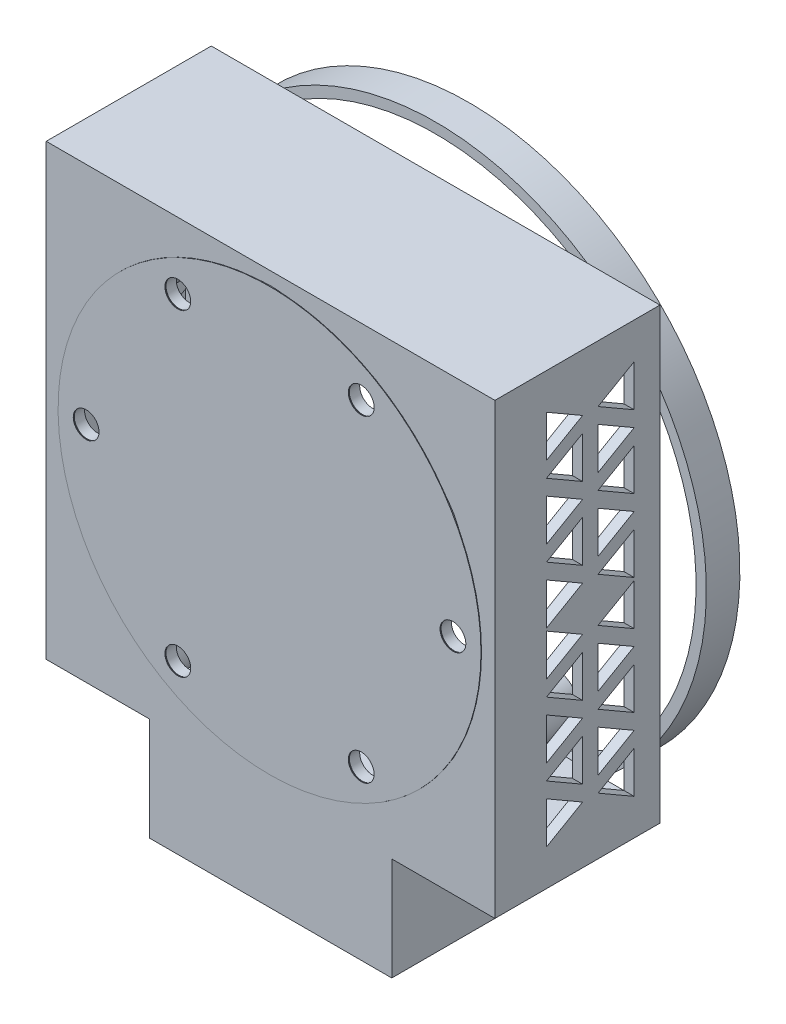
SolidWorks part; units mm, degrees
ref_plane "Front Plane" through (0, 0, 0) normal (0, 0, 1) x (1, 0, 0)
ref_plane "Top Plane" through (0, 0, 0) normal (0, 1, 0) x (1, 0, 0)
ref_plane "Right Plane" through (0, 0, 0) normal (1, 0, 0) x (0, 0, -1)
sketch "Sketch1" plane through (0, 0, 0) normal (0, 0, 1) x (1, 0, 0)
  circle A0 centre (0, 0) radius 41
  dimension "D1" = 82
extrude "Boss-Extrude1" add sketch "Sketch1" along normal blind 0.1 contours A0
sketch "Sketch2" plane through (0, 0, 0) normal (0, 0, -1) x (-1, 0, 0)
  line L0 (-35.56, 0) -> (35.56, 0) construction
  line L1 (0, 0) -> (0, -41) construction
  line L2 (0, 0) -> (0, 41) construction
  line L3 (0, -30.7959) -> (17.78, -30.7959) construction
  line L4 (0, -30.7959) -> (-17.78, -30.7959) construction
  circle A0 centre (-35.56, 0) radius 2.5
  circle A1 centre (35.56, 0) radius 2.5
  circle A2 centre (0, 0) radius 38.06 construction
  circle A3 centre (0, 0) radius 33.06 construction
  circle A4 centre (-17.78, -30.7959) radius 2.5
  circle A5 centre (17.78, -30.7959) radius 2.5
  circle A6 centre (0, 0) radius 41 construction
  circle A7 centre (-17.78, 30.7959) radius 2.5
  circle A8 centre (17.78, 30.7959) radius 2.5
  point P4 (0, 0)
  dimension "D2" = 5
  dimension "D3" = 66.12
  dimension "D4" = 76.12
  dimension "D6" = 5
  dimension "D7" = 5
  dimension "D1" = 71.12
  dimension "D5" = 35.56
extrude "Cut-Extrude1" cut sketch "Sketch2" against normal blind 10
sketch "Sketch3" plane through (0, 0, 0) normal (0, 0, -1) x (-1, 0, 0)
  circle A1 centre (0, 0) radius 47.5 construction
  arc A2 (22.2693, -27.7235) -> (12.8746, -33.1475) centre (17.78, -30.7959) ccw
  circle A3 centre (0, 0) radius 42.5 construction
  arc A5 (-12.8746, -33.1475) -> (-22.2693, -27.7235) centre (-17.78, -30.7959) ccw
  circle A12 centre (0, 0) radius 41
  arc A13 (-35.1439, -5.4241) -> (-35.1439, 5.4241) centre (-35.56, 0) ccw
  arc A14 (-22.2693, 27.7235) -> (-12.8746, 33.1475) centre (-17.78, 30.7959) ccw
  arc A15 (12.8746, 33.1475) -> (22.2693, 27.7235) centre (17.78, 30.7959) ccw
  arc A16 (35.1439, 5.4241) -> (35.1439, -5.4241) centre (35.56, 0) ccw
  arc A17 (22.2693, -27.7235) -> (35.1439, -5.4241) centre (22.9665, -13.2597) ccw
  circle A19 centre (0, 0) radius 41 construction
  arc A25 (-22.2693, 27.7235) -> (-35.1439, 5.4241) centre (-22.9665, 13.2597) ccw
  arc A26 (35.1439, 5.4241) -> (22.2693, 27.7235) centre (22.9665, 13.2597) ccw
  arc A28 (-35.1439, -5.4241) -> (-22.2693, -27.7235) centre (-22.9665, -13.2597) ccw
  arc A29 (-12.8746, -33.1475) -> (12.8746, -33.1475) centre (0, -26.5195) ccw
  arc A30 (12.8746, 33.1475) -> (-12.8746, 33.1475) centre (0, 26.5195) ccw
  dimension "D1" = 95
  dimension "D2" = 85
extrude "Boss-Extrude3" add sketch "Sketch3" along normal blind 0.1 contours A15 A30 A14 A25 A13 A28 A5 A29 A2 A17 A16 A26 region at (0, 0, 0)
sketch "Sketch4" plane through (0, 0, -0.1) normal (0, 0, -1) x (-1, 0, 0)
  line L0 (-43.5, 43.5) -> (43.5, -43.5) construction
  line L1 (-43.5, 43.5) -> (43.5, 43.5)
  line L2 (-43.5, 43.5) -> (-43.5, -43.5)
  line L3 (-43.5, -43.5) -> (43.5, -43.5)
  line L4 (43.5, 43.5) -> (43.5, -43.5)
  line L5 (-43.5, -43.5) -> (43.5, 43.5) construction
  point P2 (0, 0)
  dimension "D1" = 87
  dimension "D2" = 87
extrude "Boss-Extrude4" add sketch "Sketch4" along normal blind 2
sketch "Sketch5" plane through (0, 0, -2.1) normal (0, 0, -1) x (-1, 0, 0)
  line L1 (-43.5, 43.5) -> (43.5, 43.5)
  line L2 (-43.5, 43.5) -> (-43.5, -43.5)
  line L3 (-43.5, -43.5) -> (43.5, -43.5)
  line L4 (43.5, 43.5) -> (43.5, -43.5)
  line L5 (-41.5, 41.5) -> (41.5, 41.5)
  line L6 (-41.5, 41.5) -> (-41.5, -41.5)
  line L7 (-41.5, -41.5) -> (41.5, -41.5)
  line L8 (41.5, 41.5) -> (41.5, -41.5)
  dimension "D1" = 2
  dimension "D2" = 2
  dimension "D3" = 2
  dimension "D4" = 2
extrude "Boss-Extrude5" add sketch "Sketch5" along normal blind 30
sketch "Sketch7" plane through (0, 0, -32.1) normal (0, 0, -1) x (-1, 0, 0)
  line L1 (-41.5, 41.5) -> (41.5, 41.5)
  line L2 (-41.5, 41.5) -> (-41.5, -41.5)
  line L3 (-41.5, -41.5) -> (41.5, -41.5)
  line L4 (41.5, 41.5) -> (41.5, -41.5)
  line L5 (-43.5, 43.5) -> (43.5, 43.5)
  line L6 (-43.5, 43.5) -> (-43.5, -43.5)
  line L7 (-43.5, -43.5) -> (43.5, -43.5)
  line L8 (43.5, 43.5) -> (43.5, -43.5)
extrude "Boss-Extrude6" add sketch "Sketch7" against normal up to surface (32 mm away) up to face at (0, 0, -0.1)
sketch "Sketch8" plane through (0, 0, -32.1) normal (0, 0, -1) x (-1, 0, 0)
  line L0 (-41.5, -41.5) -> (41.5, -41.5) construction
  line L1 (41.5, -41.5) -> (41.5, 41.5) construction
  line L2 (-41.5, 41.5) -> (-41.5, -41.5) construction
  line L3 (41.5, 41.5) -> (-41.5, 41.5) construction
  line L4 (-53, 0) -> (-41.5, 0) construction
  line L5 (-41.5, 41.5) -> (-41.5, -41.5) construction
  line L6 (0, 41.5) -> (0, 53) construction
  line L7 (41.5, 0) -> (53, 0) construction
  line L8 (0, -41.5) -> (0, -53) construction
  line L9 (-41.5, -41.5) -> (41.5, -41.5) construction
  circle A0 centre (-47, 0) radius 2
  circle A1 centre (47.25, 0) radius 2
  circle A2 centre (0, 47.25) radius 2
  circle A3 centre (0, -47.25) radius 2
  circle A4 centre (-47, 0) radius 6 construction
  circle A5 centre (0, 47.25) radius 5.75 construction
  circle A6 centre (0, 0) radius 53 construction
  circle A7 centre (47.25, 0) radius 5.75 construction
  circle A8 centre (0, -47.25) radius 5.75 construction
  parabola Q1 (-50, 50) -> (-50, -50) focus (155.3333, 0) apex (-53, 0) construction
  parabola Q3 (50, 50) -> (-50, 50) focus (0, -155.3333) apex (0, 53) construction
  parabola Q4 (50, -50) -> (50, 50) focus (-155.3333, 0) apex (53, 0) construction
  parabola Q5 (-50, -50) -> (50, -50) focus (0, 155.3333) apex (0, -53) construction
  point P10 (0, -41.5)
  point P13 (41.5, 0)
  point P16 (-41.5, 0)
  point P19 (0, 41.5)
  point P50 (0, -47.25)
  point P51 (47.25, 0)
  point P52 (0, 47.25)
  dimension "D1" = 106
  dimension "D2" = 4
  dimension "D3" = 4
  dimension "D4" = 4
  dimension "D5" = 4
  dimension "D6" = 6
sketch "Sketch11" plane through (0, 0, -2.1) normal (0, 0, -1) x (-1, 0, 0)
  line L2 (0, 38.94) -> (0, 41.5) construction
  line L3 (-38.985, 38.94) -> (38.985, 38.94) construction
  line L4 (-38.985, 38.94) -> (-38.985, -38.94) construction
  line L5 (-38.985, -38.94) -> (38.985, -38.94) construction
  line L6 (38.985, 38.94) -> (38.985, -38.94) construction
  line L7 (0, -38.94) -> (0, -41.5) construction
  line L8 (-41.5, -41.5) -> (41.5, -41.5) construction
  line L9 (-38.985, 0) -> (-41.5, 0) construction
  line L10 (-41.5, 41.5) -> (-41.5, -41.5) construction
  line L11 (38.985, 0) -> (41.5, 0) construction
  line L12 (41.5, -41.5) -> (41.5, 41.5) construction
  circle A0 centre (-34.985, 34.94) radius 2
  circle A1 centre (36.985, 20.64) radius 2
  circle A2 centre (28.745, -36.94) radius 2
  circle A3 centre (-34.985, -20.58) radius 2
  circle A4 centre (-34.985, -20.58) radius 5
  circle A5 centre (28.745, -36.94) radius 5
  circle A6 centre (36.985, 20.64) radius 5
  circle A7 centre (-34.985, 34.94) radius 5
  dimension "D1" = 4
  dimension "D2" = 71.97
  dimension "D3" = 57.58
  dimension "D9" = 4
  dimension "D10" = 4
  dimension "D4" = 4
  dimension "D5" = 63.73
  dimension "D6" = 55.52
  dimension "D7" = 4
  dimension "D8" = 14.3
extrude "Boss-Extrude7" add sketch "Sketch11" along normal blind 18
sketch "Sketch10" plane through (0, 0, 0.1) normal (0, 0, 1) x (1, 0, 0)
  circle A0 centre (-17.78, 30.7959) radius 2.5
  circle A1 centre (17.78, 30.7959) radius 2.5
  circle A2 centre (35.56, 0) radius 2.5
  circle A3 centre (17.78, -30.7959) radius 2.5
  circle A4 centre (-17.78, -30.7959) radius 2.5
  circle A5 centre (-35.56, 0) radius 2.5
extrude "Cut-Extrude3" cut sketch "Sketch10" against normal through all
sketch "Sketch13" plane through (0, -43.5, 0) normal (0, -1, 0) x (1, 0, 0)
  line L0 (-53, -32.1) -> (53, -32.1) construction
  line L1 (-23.5, -0.1) -> (23.5, -0.1)
  line L2 (-23.5, -0.1) -> (-23.5, -32.1)
  line L3 (-23.5, -32.1) -> (23.5, -32.1)
  line L4 (23.5, -0.1) -> (23.5, -32.1)
  line L5 (43.5, -32.1) -> (43.5, -0.1) construction
  line L7 (-43.5, -32.1) -> (-43.5, -0.1) construction
  line L8 (43.5, -0.1) -> (-43.5, -0.1) construction
  dimension "D1" = 20
  dimension "D2" = 20
extrude "Boss-Extrude8" add sketch "Sketch13" along normal blind 20
sketch "Sketch14" plane through (0, 0, -32.1) normal (0, 0, -1) x (-1, 0, 0)
  line L1 (-19.5, -48.5) -> (19.5, -48.5)
  line L2 (-19.5, -48.5) -> (-19.5, -59.5)
  line L3 (-19.5, -59.5) -> (19.5, -59.5)
  line L4 (19.5, -48.5) -> (19.5, -59.5)
  line L5 (23.5, -63.5) -> (23.5, -43.5) construction
  line L8 (-23.5, -63.5) -> (-23.5, -43.5) construction
  line L9 (23.5, -63.5) -> (-23.5, -63.5) construction
  dimension "D1" = 4
  dimension "D2" = 4
  dimension "D3" = 4
extrude "Cut-Extrude4" cut sketch "Sketch14" against normal up to surface (30 mm away) up to face at (-38.06, 0, -2.1)
sketch "Sketch15" plane through (0, 0, -32.1) normal (0, 0, -1) x (-1, 0, 0)
  line L4 (23.5, -63.5) -> (23.5, -43.5) construction
  line L5 (23.5, -43.5) -> (43.5, -43.5) construction
  line L6 (-43.5, -43.5) -> (-23.5, -43.5) construction
  line L7 (-23.5, -63.5) -> (-23.5, -43.5) construction
  line L8 (-28.5, -55) -> (-23.5, -55)
  line L9 (-35, -48.5) -> (-35, -43.5)
  line L10 (-35, -43.5) -> (-23.5, -43.5)
  line L11 (-23.5, -43.5) -> (-23.5, -55)
  line L12 (35, -48.5) -> (35, -43.5)
  line L13 (35, -43.5) -> (23.5, -43.5)
  line L14 (23.5, -43.5) -> (23.5, -55)
  line L15 (23.5, -55) -> (28.5, -55)
  circle A0 centre (28.5, -48.5) radius 2.5
  circle A1 centre (-28.5, -48.5) radius 2.5
  arc A2 (-35, -48.5) -> (-28.5, -55) centre (-28.5, -48.5) ccw
  arc A3 (28.5, -55) -> (35, -48.5) centre (28.5, -48.5) ccw
  dimension "D1" = 4
  dimension "D2" = 4
  dimension "D3" = 5
  dimension "D4" = 5
  dimension "5" = 5
  dimension "D5" = 5
  dimension "D6" = 5
  dimension "D7" = 5
extrude "Boss-Extrude9" add sketch "Sketch15" against normal blind 10
sketch "Sketch17" plane through (0, 43.5, 0) normal (0, 1, 0) x (1, 0, 0)
  line L0 (90.9997, 294.306) -> (529.6664, 294.306) construction
sketch "Sketch18" plane through (0, 43.5, 0) normal (0, 1, 0) x (1, 0, 0)
  line L0 (-11.2864, 8.9001) -> (-10.7576, 6.864)
  line L1 (-10.7576, 6.864) -> (0.4012, 2.8447)
  line L2 (0.4012, 2.8447) -> (10.4758, 6.864)
  line L3 (10.4758, 6.864) -> (11.0046, 8.9001)
  line L4 (14.6801, 12.4169) -> (15.1825, 12.4169)
  line L5 (15.1825, 12.4169) -> (15.1825, 14.6884)
  line L6 (14.1777, 15.2463) -> (-15.9138, 15.2463)
  line L7 (-15.9138, 15.2463) -> (-15.0148, 14.0828)
  line L8 (-15.0148, 14.0828) -> (-15.0148, 9.7462)
  line L9 (-15.0148, 9.7462) -> (-15.3196, 8.9001)
  line L10 (-15.3196, 8.9001) -> (-13.8382, 8.2373)
  line L11 (-13.8382, 8.2373) -> (-11.2864, 8.9001)
  line L12 (-11.5912, 15.2463) -> (-10.2123, 18.3284)
  line L13 (-10.2123, 18.3284) -> (-12.9203, 20.2093)
  line L14 (-13.8382, 23.837) -> (-13.2786, 23.837)
  line L15 (-2.6006, 23.3686) -> (-2.4469, 24.4953)
  arc A0 (11.0046, 8.9001) -> (13.5749, 8.5717) centre (13.5749, 18.7956) ccw
  arc A1 (13.5749, 8.5717) -> (14.6801, 12.4169) centre (13.5749, 10.6531) ccw
  arc A2 (15.1825, 14.6884) -> (14.1777, 15.2463) centre (14.5253, 14.6884) ccw
  arc A3 (-12.9203, 20.2093) -> (-13.8382, 23.837) centre (-11.294, 22.5507) cw
  spline S0 degree 3 poles (-13.2786, 23.837) (-13.2351, 24.6309) (-12.1883, 24.282) (-12.2804, 23.1191) (-11.6378, 23.4778) (-11.0291, 23.0342) (-11.4314, 21.8585) (-8.6425, 20.449) (-10.7414, 22.3197) (-9.6127, 23.2158) (-9.1532, 22.3727) (-8.319, 22.2291) (-7.9837, 21.4032) (-7.3013, 20.2145) (-6.5704, 21.5122) (-5.4402, 21.9426) (-4.0464, 22.1951) (-2.0184, 22.5782) (-2.6006, 23.3686) knots 0 0 0 0 0.081998 0.113423 0.146101 0.166231 0.230517 0.331862 0.42257 0.46291 0.50183 0.555114 0.595101 0.659373 0.718216 0.780678 0.8704 1 1 1 1
sketch "Sketch20" plane through (0, 0, -32.1) normal (0, 0, -1) x (-1, 0, 0)
  circle A0 centre (0, 0) radius 52.5
  circle A1 centre (0, 0) radius 50.5
  dimension "D1" = 105
  dimension "D2" = 2
extrude "Boss-Extrude11" add sketch "Sketch20" along normal blind 6.5
sketch "Sketch21" plane through (0, 0, -32.1) normal (0, 0, -1) x (-1, 0, 0)
  line L1 (-43.5, 43.5) -> (43.5, 43.5)
  line L2 (-43.5, 43.5) -> (-43.5, -43.5)
  line L3 (-43.5, -43.5) -> (43.5, -43.5)
  line L4 (43.5, 43.5) -> (43.5, -43.5)
  circle A0 centre (0, 0) radius 50.5
  circle A2 centre (0, 0) radius 50.5 construction
extrude "Boss-Extrude12" add sketch "Sketch21" along normal blind 2 rebuild error yes
sketch "Sketch16" plane through (0, 0, -32.1) normal (0, 0, -1) x (-1, 0, 0)
  line L1 (-57.495, 6.5) -> (-50.0799, 6.5)
  line L3 (-57.495, 0) -> (57.495, 0) construction
  line L5 (57.495, 6.5) -> (50.0799, 6.5)
  line L6 (-57.495, -6.5) -> (-50.0799, -6.5)
  line L7 (57.495, -6.5) -> (50.0799, -6.5)
  line L8 (0, 50.5) -> (0, -50.5) construction
  line L9 (0, 21.285) -> (0, -21.285) construction
  line L10 (-6.5, -57.495) -> (-6.5, -50.0799)
  line L11 (6.5, -57.495) -> (6.5, -50.0799)
  line L13 (0, 57.495) -> (0, -57.495) construction
  line L14 (-6.5, 57.495) -> (-6.5, 50.0799)
  line L15 (50.5, 0) -> (57.495, 0) construction
  line L17 (6.5, 50.0799) -> (6.5, 57.495)
  circle A0 centre (-57.495, 0) radius 2.5
  circle A1 centre (57.495, 0) radius 2.5
  arc A2 (57.495, -6.5) -> (57.495, 6.5) centre (57.495, 0) ccw
  arc A3 (-57.495, 6.5) -> (-57.495, -6.5) centre (-57.495, 0) ccw
  circle A4 centre (0, 57.495) radius 2.5
  arc A5 (6.5, 57.495) -> (-6.5, 57.495) centre (0, 57.495) ccw
  arc A6 (-6.5, -50.0799) -> (6.5, -50.0799) centre (0, 0) ccw
  arc A7 (-6.5, -57.495) -> (6.5, -57.495) centre (0, -57.495) ccw
  circle A8 centre (0, -57.495) radius 2.5
  circle A9 centre (0, 0) radius 50.5 construction
  arc A10 (50.0799, -6.5) -> (50.0799, 6.5) centre (0, 0) ccw
  arc A11 (6.5, 50.0799) -> (-6.5, 50.0799) centre (0, 0) ccw
  arc A12 (-6.5, -50.0799) -> (6.5, -50.0799) centre (0, 0) ccw
  arc A13 (50.0799, -6.5) -> (50.0799, 6.5) centre (0, 0) ccw
  arc A14 (6.5, 50.0799) -> (-6.5, 50.0799) centre (0, 0) ccw
  arc A15 (-50.0799, 6.5) -> (-50.0799, -6.5) centre (0, 0) ccw
  point P11 (0, 0)
  point P26 (0, 0)
  dimension "D1" = 5
  dimension "D2" = 5
  dimension "D3" = 4
  dimension "D4" = 4
  dimension "D5" = 4
  dimension "D6" = 5
  dimension "D9" = 5
  dimension "D10" = 4
  dimension "D7" = 114.99
  dimension "D11" = 114.99
extrude "Boss-Extrude10" add sketch "Sketch16" against normal blind 10 and the other way blind 1.5 from offset 5 rebuild error yes
sketch "Sketch19" plane through (-43.5, 0, 0) normal (-1, 0, 0) x (0, 0, 1)
  line L0 (-27.1, -28.4171) -> (-27.1, -36.5)
  line L1 (-27.1, -36.5) -> (-20.1, -32.4585)
  line L2 (-20.1, -32.4585) -> (-27.1, -28.4171)
  line L3 (-27.1, -22.4171) -> (-27.1, -14.3342)
  line L4 (-27.1, -14.3342) -> (-20.1, -18.3756)
  line L5 (-20.1, -18.3756) -> (-27.1, -22.4171)
  line L6 (-20.1, -21.3756) -> (-20.1, -29.4585)
  line L7 (-20.1, -29.4585) -> (-27.1, -25.4171)
  line L8 (-27.1, -25.4171) -> (-20.1, -21.3756)
  line L12 (-17.1, -29.4585) -> (-17.1, -21.3756)
  line L13 (-17.1, -21.3756) -> (-10.1, -25.4171)
  line L14 (-10.1, -25.4171) -> (-17.1, -29.4585)
  line L15 (-10.1, -28.4171) -> (-10.1, -36.5)
  line L16 (-10.1, -36.5) -> (-17.1, -32.4585)
  line L17 (-17.1, -32.4585) -> (-10.1, -28.4171)
  line L18 (-10.1, -14.3342) -> (-10.1, -22.4171)
  line L19 (-10.1, -22.4171) -> (-17.1, -18.3756)
  line L20 (-17.1, -18.3756) -> (-10.1, -14.3342)
  line L21 (-0.1, -43.5) -> (-22.1, -43.5) construction
  line L22 (-32.1, -43.5) -> (-32.1, -29.3939) construction
  line L23 (-20.1, -7.2927) -> (-20.1, -15.3756)
  line L24 (-20.1, -15.3756) -> (-27.1, -11.3342)
  line L25 (-27.1, -11.3342) -> (-20.1, -7.2927)
  line L26 (-27.1, -8.3342) -> (-27.1, -0.2513)
  line L27 (-27.1, -0.2513) -> (-20.1, -4.2927)
  line L28 (-20.1, -4.2927) -> (-27.1, -8.3342)
  line L29 (-17.1, -15.3756) -> (-17.1, -7.2927)
  line L30 (-17.1, -7.2927) -> (-10.1, -11.3342)
  line L31 (-10.1, -11.3342) -> (-17.1, -15.3756)
  line L32 (-10.1, -0.2513) -> (-10.1, -8.3342)
  line L33 (-10.1, -8.3342) -> (-17.1, -4.2927)
  line L34 (-17.1, -4.2927) -> (-10.1, -0.2513)
  dimension "D1" = 7
  dimension "D2" = 3
  dimension "D3" = 3
  dimension "D4" = 7
  dimension "D5" = 3
  dimension "D6" = 3
  dimension "D8" = 7
  dimension "D9" = 5
  dimension "D10" = 3
  dimension "D11" = 3
  dimension "D12" = 3
  dimension "D13" = 3
  dimension "D14" = 3
  dimension "D15" = 3
extrude "Cut-Extrude5" cut sketch "Sketch19" against normal blind 2
mirror "Mirror1" about plane through (0, 0, 0) normal (0, 1, 0) of "Cut-Extrude5"
mirror "Mirror2" about plane through (0, 0, 0) normal (1, 0, 0) of "Mirror1", "Cut-Extrude5"
